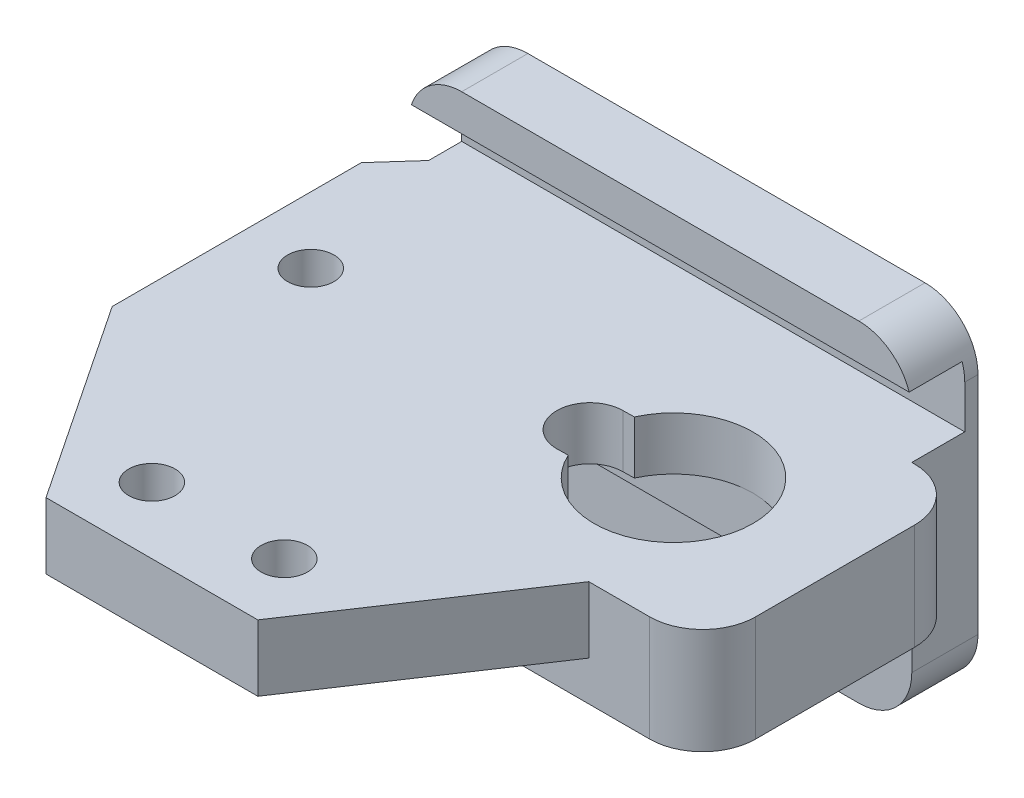
SolidWorks part; units mm, degrees
ref_plane "Front Plane" through (0, 0, 0) normal (0, 0, 1) x (1, 0, 0)
ref_plane "Top Plane" through (0, 0, 0) normal (0, 1, 0) x (1, 0, 0)
ref_plane "Right Plane" through (0, 0, 0) normal (1, 0, 0) x (0, 0, -1)
sketch "Sketch1" plane through (0, 0, 0) normal (0, 1, 0) x (1, 0, 0)
  line L0 (0, 33.8197) -> (10, 45)
  line L1 (0, 0) -> (60, 0)
  line L2 (0, 0) -> (0, 45)
  line L3 (0, 45) -> (60, 45)
  line L4 (60, 0) -> (60, 45)
  line L5 (0, 15) -> (10, 0)
  line L6 (26, 45) -> (36, 35)
  line L7 (26, 0) -> (36, 15)
  line L8 (36, 15) -> (60, 15)
  line L9 (1.0557, 35) -> (60, 35)
  circle A0 centre (5, 25) radius 1.75
  circle A1 centre (13, 5) radius 1.75
  circle A2 centre (23, 5) radius 1.75
  dimension "D14" = 3.5
  dimension "D15" = 10
  dimension "D16" = 3.5
  dimension "D24" = 3
  dimension "D25" = 3
  dimension "D17" = 3.5
  dimension "D1" = 45
  dimension "D2" = 60
  dimension "D3" = 15
  dimension "D4" = 10
  dimension "D5" = 10
  dimension "D6" = 15
  dimension "D7" = 16
  dimension "D8" = 16
  dimension "D9" = 10
  dimension "D10" = 10
  dimension "D11" = 10
  dimension "D12" = 20
  dimension "D18" = 5
  dimension "D19" = 5
extrude "Boss-Extrude1" add sketch "Sketch1" along normal blind 5 contours L4 A0 L2 L5 L1 L7 L8 | L4 L9 L6 L3 L0 L2 A0 region at (27.3149, 0, -21.1095) region at (18.2966, 0, -39.3802)
sketch "Sketch3" plane through (0, 0, 0) normal (0, -1, 0) x (1, 0, 0)
  line L0 (36, -15) -> (60, -15) construction
  line L1 (15.8001, -31) -> (38.4001, -31)
  line L2 (15.8001, -31) -> (15.8001, -19)
  line L3 (15.8001, -19) -> (38.4001, -19)
  line L4 (38.4001, -31) -> (38.4001, -19)
  line L5 (15.8001, -31) -> (38.4001, -19) construction
  line L6 (15.8001, -19) -> (38.4001, -31) construction
  line L7 (9.6001, -35) -> (44.6001, -35)
  line L8 (9.6001, -35) -> (9.6001, -15)
  line L9 (9.6001, -15) -> (44.6001, -15)
  line L10 (44.6001, -35) -> (44.6001, -15)
  line L11 (9.6001, -35) -> (44.6001, -15) construction
  line L12 (9.6001, -15) -> (44.6001, -35) construction
  line L14 (15.8001, -19) -> (9.6001, -19)
  line L15 (15.8001, -19) -> (15.8001, -31)
  line L16 (15.8001, -31) -> (9.6001, -31)
  line L17 (9.6001, -19) -> (9.6001, -31)
  line L18 (38.4001, -31) -> (44.6001, -31)
  line L19 (38.4001, -31) -> (38.4001, -19)
  line L20 (38.4001, -19) -> (44.6001, -19)
  line L21 (44.6001, -31) -> (44.6001, -19)
  point P0 (27.1001, -25)
  point P10 (27.1001, -25)
  dimension "D3" = 4
  dimension "D1" = 22.6
  dimension "D2" = 12
  dimension "D4" = 6.2
extrude "Boss-Extrude4" add sketch "Sketch3" along normal blind 3 contours L16 L2 L14 L8 | L20 L19 L4 L18 L10 | L8 L10 L18 L1 L16 | L3 L20 L10 L8 L14 region at (12.7001, 0, -25) region at (27.1001, 0, -33) region at (41.5001, 0, -25) region at (27.1001, 0, -17)
sketch "Sketch6" plane through (0, 0, 0) normal (0, -1, 0) x (1, 0, 0)
  line L3 (44.6001, -15) -> (44.6001, -35)
  line L4 (44.6001, -35) -> (60, -35)
  line L5 (60, -15) -> (44.6001, -15)
  line L6 (44.6001, -15) -> (44.6001, -35)
  line L7 (44.6001, -35) -> (60, -35)
  line L8 (60, -15) -> (44.6001, -15)
  line L10 (60, -35) -> (60, -15)
  line L11 (60, -35) -> (60, -15)
  dimension "D1" = 0
extrude "Cut-Extrude2" cut sketch "Sketch6" against normal through all
sketch "Sketch9" plane through (0, -3, 0) normal (0, -1, 0) x (1, 0, 0)
  line L0 (15.8001, -31) -> (15.8001, -19) construction
  line L2 (15.8001, -25) -> (18.2774, -25) construction
  circle A0 centre (13.5251, -25) radius 1
  circle A1 centre (40.6751, -25) radius 1
  dimension "D1" = 2
  dimension "D2" = 2
  dimension "D3" = 27.15
  dimension "D4" = 2.275
extrude "Cut-Extrude4" cut sketch "Sketch9" against normal blind 7
sketch "Sketch24" plane through (0, 0, -35) normal (0, 0, -1) x (-1, 0, 0)
  line L9 (-36, 5) -> (-44.6001, 5) construction
  line L11 (-40.4, 12.25) -> (-2.4, 12.25)
  line L12 (-40.4, 12.25) -> (-40.4, -12.75)
  line L13 (-40.4, -12.75) -> (-2.4, -12.75)
  line L14 (-2.4, 12.25) -> (-2.4, -12.75)
  dimension "D1" = 25
  dimension "D2" = 38
  dimension "D3" = 7.25
extrude "Boss-Extrude8" add sketch "Sketch24" along normal blind 5
sketch "Sketch27" plane through (0, 0, -40) normal (0, 0, -1) x (-1, 0, 0)
  circle A0 centre (-21.4, -0.25) radius 2.3
  dimension "D1" = 4.6
extrude "Cut-Extrude15" cut sketch "Sketch27" against normal blind 4
fillet "Fillet9" radius 4 6 edges at (44.6001, 1, -35) (44.6001, 1, -15) (2.4, 12.25, -37.5) (2.4, -12.75, -37.5) (40.4, 12.25, -37.5) (40.4, -12.75, -37.5)
extrude "Cut-Extrude16" cut sketch "Sketch3<5>" against normal blind 3 contours L1 L4 L3 L2 region at (27.1001, 0, -25)
sketch "Sketch3<5>" plane through (0, 0, 0) normal (0, -1, 0) x (1, 0, 0) same geometry as "Sketch3"
sketch "Sketch34" plane through (0, 3, 0) normal (0, -1, 0) x (1, 0, 0)
  line L7 (15.8001, -19) -> (15.8001, -31) construction
  line L9 (38.4001, -31) -> (44.4001, -31)
  line L10 (44.4001, -31) -> (44.4001, -25)
  line L11 (44.4001, -25) -> (44.4001, -19)
  line L12 (44.4001, -19) -> (38.4001, -19)
  line L15 (38.4001, -19) -> (15.8001, -19)
  line L16 (15.8001, -19) -> (15.8001, -31)
  line L17 (15.8001, -31) -> (38.4001, -31)
extrude "Boss-Extrude9" add sketch "Sketch34" along normal blind 2
sketch "Sketch35" plane through (0, 1, 0) normal (0, -1, 0) x (1, 0, 0)
  line L0 (26.1003, -22.4823) -> (26.9458, -22.5)
  line L1 (26.1003, -27.4823) -> (26.9458, -27.5)
  arc A0 (26.1003, -27.4823) -> (26.1003, -22.4823) centre (26.1003, -24.9823) cw
  arc A1 (26.9458, -27.5) -> (26.9458, -22.5) centre (32.4001, -25) ccw
  dimension "D2" = 2.5
  dimension "D3" = 12
  dimension "D1" = 6.2998
  dimension "D4" = 0.8455
  dimension "D5" = 0.8455
extrude "Cut-Extrude18" cut sketch "Sketch35" against normal blind 4
sketch "Sketch36" plane through (0, 5, 0) normal (0, 1, 0) x (1, 0, 0)
  line L4 (5.5279, 40) -> (31, 40)
  line L5 (31, 40) -> (26, 45)
  line L6 (26, 45) -> (10, 45)
  line L7 (10, 45) -> (5.5279, 40)
  line L8 (5.5279, 40) -> (31, 40)
  line L9 (31, 40) -> (26, 45)
  line L10 (26, 45) -> (10, 45)
  line L11 (10, 45) -> (5.5279, 40)
  dimension "D1" = 0
extrude "Cut-Extrude19" cut sketch "Sketch36" against normal through all
sketch "Sketch37" plane through (0, 0, -35) normal (0, 0, 1) x (1, 0, 0)
  line L1 (2.4, 5) -> (40.4, 5)
  line L2 (2.4, 5) -> (2.4, 9.5)
  line L3 (2.4, 9.5) -> (40.4, 9.5)
  line L4 (40.4, 5) -> (40.4, 9.5)
  dimension "D1" = 4.5
extrude "Cut-Extrude20" cut sketch "Sketch37" against normal blind 4 contours L3 L4 L1 L2
